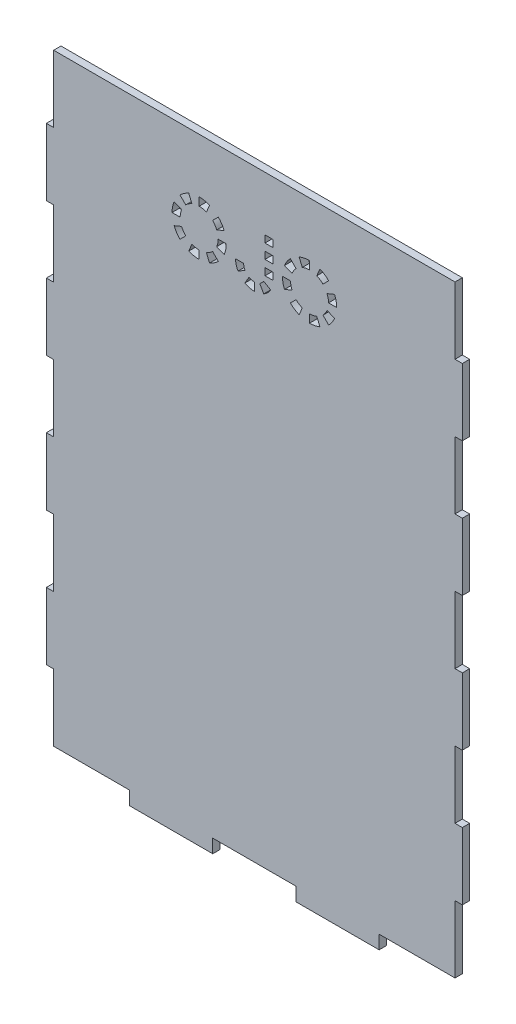
SolidWorks part; units mm, degrees
ref_plane "Ön Düzlem" through (0, 0, 0) normal (0, 0, 1) x (1, 0, 0)
ref_plane "Üst Düzlem" through (0, 0, 0) normal (0, 1, 0) x (1, 0, 0)
ref_plane "Sağ Düzlem" through (0, 0, 0) normal (1, 0, 0) x (0, 0, -1)
sketch "Sketch1" plane through (0, 0, 0) normal (0, 0, 1) x (1, 0, 0)
  line L0 (46.02, -108.65) -> (74, -108.65)
  line L3 (74, 113.65) -> (-74, 113.65)
  line L5 (73.3256, -108.65) -> (-74, 109.6493) construction
  line L6 (74, 109.6493) -> (-73.3256, -108.65) construction
  line L7 (-74, -108.65) -> (-46.02, -108.65)
  line L8 (-15.34, -108.65) -> (15.34, -108.65)
  line L9 (-74, -108.65) -> (-74, -83.95)
  line L11 (74, -108.65) -> (74, -83.95)
  line L13 (-74, -59.25) -> (-74, -34.55)
  line L15 (-74, -9.85) -> (-74, 14.85)
  line L16 (-76.7, 14.85) -> (-76.7, 39.55)
  line L17 (-74, 39.55) -> (-74, 64.25)
  line L18 (-76.7, -34.55) -> (-76.7, -9.85)
  line L19 (-74, 88.95) -> (-74, 113.65)
  line L20 (76.7, -34.55) -> (76.7, -9.85)
  line L21 (74, -59.25) -> (74, -34.55)
  line L22 (76.7, 14.85) -> (76.7, 39.55)
  line L23 (74, -9.85) -> (74, 14.85)
  line L24 (76.7, 64.25) -> (76.7, 88.95)
  line L25 (74, 39.55) -> (74, 64.25)
  line L26 (46.02, -113.65) -> (15.34, -113.65)
  line L27 (74, 88.95) -> (74, 113.65)
  line L28 (-74, 88.95) -> (-76.7, 88.95)
  line L29 (-74, 64.25) -> (-76.7, 64.25)
  line L30 (-74, 39.55) -> (-76.7, 39.55)
  line L31 (-74, 14.85) -> (-76.7, 14.85)
  line L32 (-74, -9.85) -> (-76.7, -9.85)
  line L33 (-74, -34.55) -> (-76.7, -34.55)
  line L34 (-74, -83.95) -> (-76.7, -83.95)
  line L35 (74, -83.95) -> (76.7, -83.95)
  line L36 (74, 88.95) -> (76.7, 88.95)
  line L37 (74, 64.25) -> (76.7, 64.25)
  line L38 (74, 39.55) -> (76.7, 39.55)
  line L39 (74, 14.85) -> (76.7, 14.85)
  line L40 (74, -9.85) -> (76.7, -9.85)
  line L41 (74, -34.55) -> (76.7, -34.55)
  line L42 (74, -59.25) -> (76.7, -59.25)
  line L43 (-76.7, 64.25) -> (-76.7, 88.95)
  line L44 (-76.7, -83.95) -> (-76.7, -61.75)
  line L45 (76.7, -83.95) -> (76.7, -59.25)
  line L46 (-74, -59.25) -> (-76.7, -59.25)
  line L47 (-15.34, -113.65) -> (-46.02, -113.65)
  line L48 (-76.7, -61.75) -> (-76.7, -59.25)
  line L49 (-46.02, -113.65) -> (-46.02, -108.65)
  line L50 (-15.34, -113.65) -> (-15.34, -108.65)
  line L51 (15.34, -113.65) -> (15.34, -108.65)
  line L52 (46.02, -113.65) -> (46.02, -108.65)
  line L63 (-13.2808, 76.5789) -> (-15.4021, 78.7003)
  line L64 (-11.113, 79.8232) -> (-13.8847, 80.9712)
  line L65 (-10.3518, 83.65) -> (-13.3518, 83.65)
  line L66 (-11.113, 87.4768) -> (-13.8847, 86.3288)
  line L67 (-13.2808, 90.7211) -> (-15.4021, 88.5997)
  line L68 (-16.525, 92.8888) -> (-17.673, 90.1172)
  line L69 (-20.3518, 93.65) -> (-20.3518, 90.65)
  line L70 (-23.0306, 90.1172) -> (-24.1787, 92.8888)
  line L71 (-25.3016, 88.5997) -> (-27.4229, 90.7211)
  line L72 (-26.819, 86.3288) -> (-29.5906, 87.4768)
  line L73 (-27.3518, 83.65) -> (-30.3518, 83.65)
  line L74 (-26.819, 80.9712) -> (-29.5906, 79.8232)
  line L75 (-25.3016, 78.7003) -> (-27.4229, 76.5789)
  line L76 (-23.0306, 77.1828) -> (-24.1787, 74.4112)
  line L77 (-20.3518, 76.65) -> (-20.3518, 73.65)
  line L78 (-16.525, 74.4112) -> (-17.673, 77.1828)
  line L79 (23.0306, 77.1828) -> (24.1787, 74.4112)
  line L80 (20.3518, 76.65) -> (20.3518, 73.65)
  line L81 (26.819, 80.9712) -> (29.5906, 79.8232)
  line L82 (25.3016, 78.7003) -> (27.4229, 76.5789)
  line L83 (26.819, 86.3288) -> (29.5906, 87.4768)
  line L84 (27.3518, 83.65) -> (30.3518, 83.65)
  line L85 (23.0306, 90.1172) -> (24.1787, 92.8888)
  line L86 (25.3016, 88.5997) -> (27.4229, 90.7211)
  line L87 (16.525, 92.8888) -> (17.673, 90.1172)
  line L88 (20.3518, 93.65) -> (20.3518, 90.65)
  line L89 (11.113, 87.4768) -> (13.8847, 86.3288)
  line L90 (13.2808, 90.7211) -> (15.4021, 88.5997)
  line L91 (11.113, 79.8232) -> (13.8847, 80.9712)
  line L92 (10.3518, 83.65) -> (13.3518, 83.65)
  line L93 (13.2808, 76.5789) -> (15.4021, 78.7003)
  line L94 (16.525, 74.4112) -> (17.673, 77.1828)
  line L98 (-6.9421, 80.5931) -> (-3.939, 80.5931)
  line L100 (6.944, 93.65) -> (3.9304, 93.65)
  line L101 (3.941, 80.5931) -> (3.9388, 83.2044)
  line L102 (6.944, 80.5931) -> (6.944, 83.2044)
  line L103 (3.9367, 85.8158) -> (3.9346, 88.4272)
  line L105 (3.9325, 91.0386) -> (3.9304, 93.65)
  line L106 (3.9325, 91.0386) -> (6.944, 91.0386)
  line L107 (3.9346, 88.4272) -> (6.944, 88.4272)
  line L108 (3.9367, 85.8158) -> (6.944, 85.8158)
  line L109 (3.9388, 83.2044) -> (6.944, 83.2044)
  line L110 (3.941, 80.5931) -> (6.944, 80.5931)
  line L111 (-3.4112, 78.6231) -> (-6.0119, 77.1215)
  line L112 (-3.4706, 74.5802) -> (-1.969, 77.1809)
  line L113 (0.001, 76.6531) -> (0.001, 73.65)
  line L114 (3.4725, 74.5802) -> (1.971, 77.1809)
  line L115 (6.0138, 77.1215) -> (3.4131, 78.6231)
  line L117 (6.944, 91.0386) -> (6.944, 93.65)
  line L118 (6.944, 85.8158) -> (6.944, 88.4272)
  arc A0 (-11.113, 87.4768) -> (-13.2808, 90.7211) centre (-20.3518, 83.65) ccw
  arc A3 (-23.0306, 90.1172) -> (-25.3016, 88.5997) centre (-20.3518, 83.65) ccw
  arc A5 (-16.525, 92.8888) -> (-20.3518, 93.65) centre (-20.3518, 83.65) ccw
  arc A7 (-24.1787, 92.8888) -> (-27.4229, 90.7211) centre (-20.3518, 83.65) ccw
  arc A9 (-29.5906, 87.4768) -> (-30.3518, 83.65) centre (-20.3518, 83.65) ccw
  arc A11 (-29.5906, 79.8232) -> (-27.4229, 76.5789) centre (-20.3518, 83.65) ccw
  arc A13 (-24.1787, 74.4112) -> (-20.3518, 73.65) centre (-20.3518, 83.65) ccw
  arc A15 (-16.525, 74.4112) -> (-13.2808, 76.5789) centre (-20.3518, 83.65) ccw
  arc A17 (-11.113, 79.8232) -> (-10.3518, 83.65) centre (-20.3518, 83.65) ccw
  arc A19 (-17.673, 90.1172) -> (-20.3518, 90.65) centre (-20.3518, 83.65) ccw
  arc A20 (-13.8847, 86.3288) -> (-15.4021, 88.5997) centre (-20.3518, 83.65) ccw
  arc A21 (-13.8847, 80.9712) -> (-13.3518, 83.65) centre (-20.3518, 83.65) ccw
  arc A22 (-17.673, 77.1828) -> (-15.4021, 78.7003) centre (-20.3518, 83.65) ccw
  arc A23 (-23.0306, 77.1828) -> (-20.3518, 76.65) centre (-20.3518, 83.65) ccw
  arc A24 (-26.819, 80.9712) -> (-25.3016, 78.7003) centre (-20.3518, 83.65) ccw
  arc A25 (-26.819, 86.3288) -> (-27.3518, 83.65) centre (-20.3518, 83.65) ccw
  arc A26 (23.0306, 77.1828) -> (20.3518, 76.65) centre (20.3518, 83.65) cw
  arc A27 (24.1787, 74.4112) -> (20.3518, 73.65) centre (20.3518, 83.65) cw
  arc A28 (26.819, 80.9712) -> (25.3016, 78.7003) centre (20.3518, 83.65) cw
  arc A29 (29.5906, 79.8232) -> (27.4229, 76.5789) centre (20.3518, 83.65) cw
  arc A30 (26.819, 86.3288) -> (27.3518, 83.65) centre (20.3518, 83.65) cw
  arc A31 (29.5906, 87.4768) -> (30.3518, 83.65) centre (20.3518, 83.65) cw
  arc A32 (23.0306, 90.1172) -> (25.3016, 88.5997) centre (20.3518, 83.65) cw
  arc A33 (24.1787, 92.8888) -> (27.4229, 90.7211) centre (20.3518, 83.65) cw
  arc A34 (16.525, 92.8888) -> (20.3518, 93.65) centre (20.3518, 83.65) cw
  arc A35 (17.673, 90.1172) -> (20.3518, 90.65) centre (20.3518, 83.65) cw
  arc A36 (11.113, 87.4768) -> (13.2808, 90.7211) centre (20.3518, 83.65) cw
  arc A37 (13.8847, 86.3288) -> (15.4021, 88.5997) centre (20.3518, 83.65) cw
  arc A38 (11.113, 79.8232) -> (10.3518, 83.65) centre (20.3518, 83.65) cw
  arc A39 (13.8847, 80.9712) -> (13.3518, 83.65) centre (20.3518, 83.65) cw
  arc A40 (16.525, 74.4112) -> (13.2808, 76.5789) centre (20.3518, 83.65) cw
  arc A41 (17.673, 77.1828) -> (15.4021, 78.7003) centre (20.3518, 83.65) cw
  arc A43 (-6.9421, 80.5931) -> (-6.0119, 77.1215) centre (0.001, 80.5931) ccw
  arc A44 (-3.939, 80.5931) -> (-3.4112, 78.6231) centre (0.001, 80.5931) ccw
  arc A46 (-3.4706, 74.5802) -> (0.001, 73.65) centre (0.001, 80.5931) ccw
  arc A48 (3.4725, 74.5802) -> (6.0138, 77.1215) centre (0.001, 80.5931) ccw
  arc A50 (1.971, 77.1809) -> (3.4131, 78.6231) centre (0.001, 80.5931) ccw
  arc A51 (-1.969, 77.1809) -> (0.001, 76.6531) centre (0.001, 80.5931) ccw
  point P0 (0, 0)
extrude "Boss-Extrude2" add sketch "Sketch1" along normal blind 2.7
